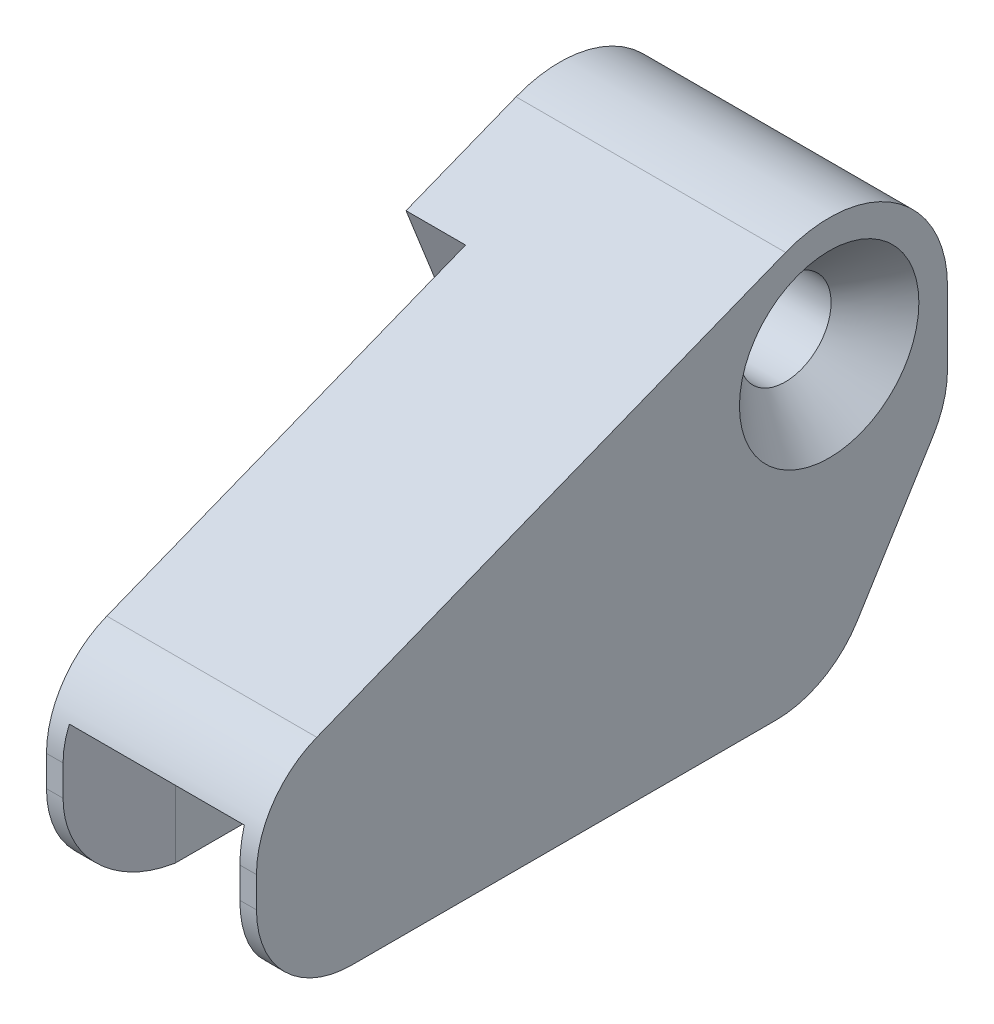
SolidWorks part; units mm, degrees
ref_plane "Front Plane" through (0, 0, 0) normal (0, 0, 1) x (1, 0, 0)
ref_plane "Top Plane" through (0, 0, 0) normal (0, 1, 0) x (1, 0, 0)
ref_plane "Right Plane" through (0, 0, 0) normal (1, 0, 0) x (0, 0, -1)
sketch "Sketch1" plane through (0, 0, 0) normal (1, 0, 0) x (0, 0, -1)
  line L1 (-30, -15.2) -> (-30, -5.2)
  line L2 (-30, -5.2) -> (-2.2807, 5.7653)
  line L5 (6.2, 0) -> (6.2, -5.2)
  line L7 (6.2, -5.2) -> (0, -15.2)
  line L8 (0, -15.2) -> (-30, -15.2)
  circle A0 centre (0, 0) radius 2.2
  arc A2 (6.2, 0) -> (-2.2807, 5.7653) centre (0, 0) ccw
  point P9 (6.2, 0)
  dimension "D1" = 4.4
  dimension "D2" = 10
  dimension "D4" = 4
  dimension "D3" = 30
  dimension "D5" = 3
  dimension "D7" = 10
extrude "Boss-Extrude1" add sketch "Sketch1" along normal blind 11
sketch "Sketch2" plane through (0, 0, 30) normal (0, 0, 1) x (1, 0, 0)
  line L0 (11, -15.2) -> (0, -15.2) construction
  line L1 (1.75, -15.2) -> (9.25, -15.2)
  line L2 (1.75, -15.2) -> (1.75, -6.95)
  line L3 (1.75, -6.95) -> (9.25, -6.95)
  line L4 (9.25, -15.2) -> (9.25, -6.95)
  line L5 (0, -5.2) -> (11, -15.2) construction
  line L6 (0, -15.2) -> (11, -5.2) construction
  line L7 (9.25, -11.075) -> (11, -11.075) construction
  line L8 (11, -5.2) -> (11, -15.2) construction
  line L9 (5.5, -6.95) -> (5.5, -5.2) construction
  line L10 (11, -5.2) -> (0, -5.2) construction
  point P17 (5.5, -6.95)
  point P18 (5.5, -10.2)
  dimension "D1" = 7.5
  dimension "D2" = 8.25
extrude "Cut-Extrude1" cut sketch "Sketch2" against normal up to surface (30 mm away) up to face at (5.5, -10.2, -3.1)
chamfer "Chamfer3" distance 5 angle 10 2 edges at (9.25, -11.075, 30) (1.75, -11.075, 30) first distance on face at (9.25, -11.075, 13.7212) first distance on face at (1.75, -11.075, 13.7212)
fillet "Fillet1" radius 5 6 edges at (0.4342, -15.2, 30) (10.5658, -15.2, 30) (5.5, -5.2, -6.2) (0.875, -15.2, 0) (10.125, -15.2, 0) (5.5, -5.2, 30)
chamfer "Chamfer1" distance 4 angle 20 1 edges at (5.5, -6.95, -5.115) first distance on face at (5.5, -9.7575, -3.3744)
hole_wizard "CSK for M4 Flat Head Machine Screw1" positions "Sketch3" profile "Sketch5" countersink size "M4" standard "ANSI Metric" end condition through all
sketch "Sketch3" plane through (11, 0, 0) normal (1, 0, 0) x (0, 0, -1)
  point P0 (0, 0)
sketch "Sketch5" plane through (11, 0, 0) normal (0, 1, 0) x (0, 0, -1)
  line L0 (0, 0) -> (0, 11)
  line L1 (0, 11) -> (2.4, 11)
  line L2 (2.4, 11) -> (2.4, 2.3)
  line L3 (2.4, 2.3) -> (4.7, 0)
  line L5 (4.7, 0) -> (0, 0)
  line L6 (-2.4, 2.3) -> (-4.7, 0) construction
  line L11 (0, -6.35) -> (0, 107.95) construction
  dimension "Thru Hole Dia." = 4.8
  dimension "Thru Hole Depth" = 11
  dimension "Near C'Sink Dia." = 9.4
  dimension "Near C'Sink Angle" = 90
sketch "Sketch6" plane through (0, 0, 0) normal (-1, 0, 0) x (0, 0, 1)
  line L0 (8.0459, 3.4846) -> (5.7653, -2.2807)
  line L1 (2.2807, 5.7653) -> (26.8392, -3.9497) construction
  line L2 (8.0459, 3.4846) -> (2.2807, 5.7653)
  arc A0 (2.2807, 5.7653) -> (5.7653, -2.2807) centre (0, 0) ccw
  circle A1 centre (0, 0) radius 2.4
  arc A2 (2.2807, 5.7653) -> (-6.2, 0) centre (0, 0) ccw construction
  circle A3 centre (0, 0) radius 2.4 construction
extrude "Boss-Extrude2" add sketch "Sketch6" along normal blind 3.12
